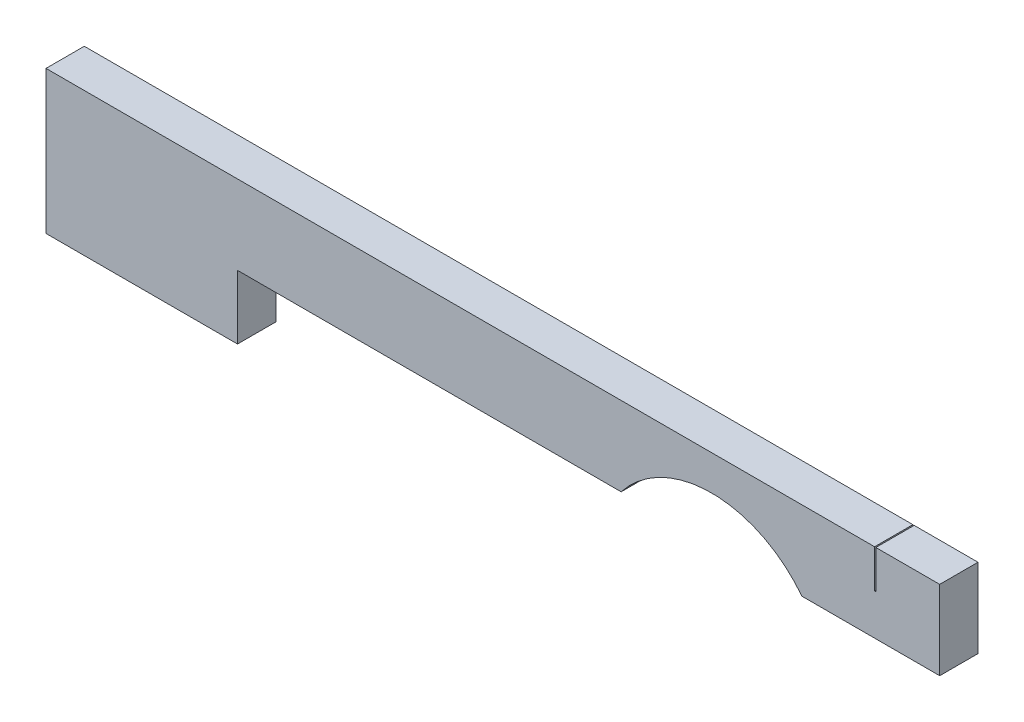
SolidWorks part; units mm, degrees
ref_plane "Front Plane" through (0, 0, 0) normal (0, 0, 1) x (1, 0, 0)
ref_plane "Top Plane" through (0, 0, 0) normal (0, 1, 0) x (1, 0, 0)
ref_plane "Right Plane" through (0, 0, 0) normal (1, 0, 0) x (0, 0, -1)
sketch "Sketch1" plane through (0, 0, 0) normal (0, 0, 1) x (1, 0, 0)
  line L0 (0, 0) -> (0, 11.2)
  line L1 (0, 11.2) -> (70, 11.2)
  line L2 (70, 11.2) -> (70, 5)
  line L3 (70, 5) -> (15, 5)
  line L4 (15, 5) -> (15, 0)
  line L5 (15, 0) -> (0, 0)
  dimension "D2" = 15
  dimension "D3" = 6.2
  dimension "D4" = 70
extrude "Boss-Extrude1" add sketch "Sketch1" along normal blind 3
sketch "Sketch3" plane through (0, 11.2, 0) normal (0, 1, 0) x (1, 0, 0)
  line L0 (0, -1.5) -> (64.95, -1.5) construction
  line L1 (0, -3) -> (0, 0) construction
  line L2 (70, 0) -> (0, 0) construction
  line L3 (64.9, -3) -> (65, -3)
  line L4 (64.9, -3) -> (64.9, 0)
  line L5 (64.9, 0) -> (65, 0)
  line L6 (65, -3) -> (65, 0)
  line L7 (64.9, -3) -> (65, 0) construction
  line L8 (64.9, 0) -> (65, -3) construction
  dimension "D1" = 64.95
extrude "Cut-Extrude1" cut sketch "Sketch3" against normal blind 3
sketch "Sketch4" plane through (0, 0, 3) normal (0, 0, 1) x (1, 0, 0)
  circle A1 centre (52.1288, -0.4941) radius 8.9613
extrude "Cut-Extrude2" cut sketch "Sketch4" against normal blind 10
equation "\"A.L\"= 0.06m"
equation "\"A.h\"= 0.005m"
equation "\"A.d\"= 0.003m"
equation "\"A.delta\"= 45.0001"
equation "\"A.w\"= 0.02m"
equation "\"A.v\"= 0.03m"
equation "\"A.s\"= 0.0075m"
equation "\"A.t\"= 0.005m"
equation "\"B.L\"= 0.04m"
equation "\"B.h\"= 0.004m"
equation "\"B.s\"= 0.008m"
equation "\"B.t\"= 0.004m"
equation "\"C.h\"= 0.0062m"
equation "\"C.d\"= 0.003m"
equation "\"C.L\"= 0.05m"
equation "\"C.wmax\"= 0.005m"
equation "\"D.L\"= 0.045m"
equation "\"D.h\"= 0.004m"
equation "\"D.s\"= 0.01m"
equation "\"D.t\"= 0.004m"
equation "\"a_h\"= 0.0001m"
equation "\"a_d\"= 0.003m"
equation "\"a_L\"= 0.01m"
equation "\"b_h\"= 0.0004m"
equation "\"b_d\"= 0.003m"
equation "\"b_L\"= 0.01m"
equation "\"c_h\"= 0.0001m"
equation "\"c_d\"= 0.003m"
equation "\"c_L\"= 0.01m"
equation "\"d_h\"= 0.0001m"
equation "\"d_d\"= 0.003m"
equation "\"d_L\"= 0.01m"
equation "\"S.h\"= 0.015m"
equation "\"S.L\"= 0.0559m"
equation "\"D1@Sketch1\"=\"C.h\"+\"C.wmax\""
equation "\"D2@Sketch1\"=\"S.h\""
equation "\"D3@Sketch1\"=\"C.h\""
equation "\"D4@Sketch1\"=\"C.L\"+\"S.h\"+0.005"
equation "\"D1@Boss-Extrude1\"=\"C.d\""
equation "\"D1@Sketch3\"=\"C.L\"+\"S.h\"-\"c_h\"/2"
equation "\"D2@Sketch3\"=\"c_h\""
